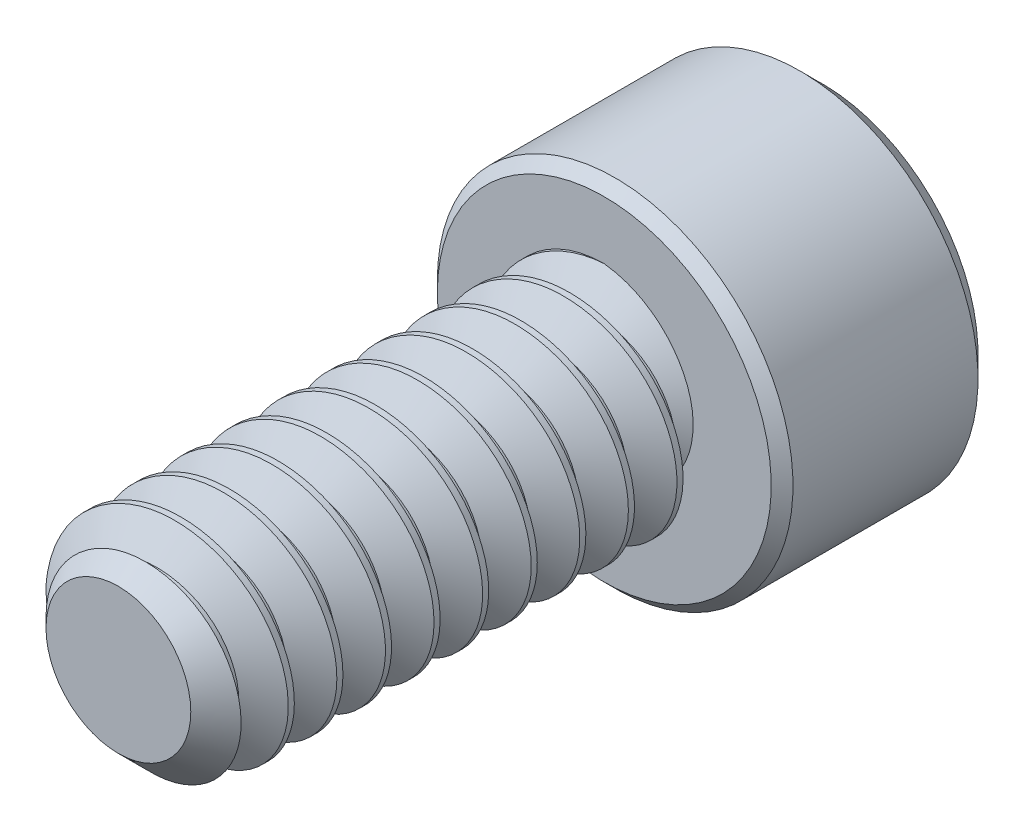
SolidWorks part; units mm, degrees
material "Alloy Steel"
ref_plane "Front Plane" through (0, 0, 0) normal (0, 0, 1) x (1, 0, 0)
ref_plane "Top Plane" through (0, 0, 0) normal (0, 1, 0) x (1, 0, 0)
ref_plane "Right Plane" through (0, 0, 0) normal (1, 0, 0) x (0, 0, -1)
sketch "Sketch1" plane through (0, 0, 0) normal (0, 0, 1) x (1, 0, 0)
  line L0 (0, 1.4224) -> (0, -1.4224) construction
  circle A0 centre (0, 0) radius 1.4224
  dimension "OD" = 2.8448
extrude "Extrude1" add sketch "Sketch1" against normal blind 6.35
sketch "Sketch2" plane through (0, 0, 0) normal (0, 0, 1) x (1, 0, 0)
  circle A0 centre (0, 0) radius 1.4224 construction
  circle A1 centre (0, 0) radius 1.4224
curve "Helix/Spiral1" pitch 0.635 height 6.985 radius 1.4224 centre (0, 0, 0) axis (0, 0, -1) start towards (0, 1, 0) parameters "pitch"=0.635
chamfer "Chamfer3" distance 0.4763 angle 45 1 edges at (1.4224, 0, 0)
sketch "Sketch3" plane through (0, 0, 0) normal (1, 0, 0) x (0, 0, -1)
  line L0 (-0.5556, 1.4224) -> (-0.3175, 1.01)
  line L1 (-0.3175, 1.01) -> (-0.2381, 1.01)
  line L2 (-0.2381, 1.01) -> (0, 1.4224)
  line L3 (-0.5556, 1.4224) -> (0, 1.4224)
  line L4 (-0.2778, 1.4224) -> (-0.2778, 1.01) construction
  line L5 (-0.4366, 1.2162) -> (-0.1191, 1.2162) construction
  line L6 (0, 1.4224) -> (0, -1.4224) construction
  dimension "D1" = 0.0794
  dimension "D2" = 0.3175
  dimension "D3" = 60
sweep "Cut-Sweep1" cut profiles "Sketch3" path "Helix/Spiral1"
sketch "Sketch6" plane through (0, 0, -6.35) normal (0, 0, -1) x (-1, 0, 0)
  circle A0 centre (0, 0) radius 2.3241
  dimension "head dia" = 4.6482
extrude "Extrude2" add sketch "Sketch6" along normal blind 2.8448
sketch "Sketch7" plane through (0, 0, -9.1948) normal (0, 0, -1) x (-1, 0, 0)
  line L1 (0, 1.3748) -> (-1.1906, 0.6874)
  line L2 (-1.1906, 0.6874) -> (-1.1906, -0.6874)
  line L3 (-1.1906, -0.6874) -> (0, -1.3748)
  line L4 (0, -1.3748) -> (1.1906, -0.6874)
  line L5 (1.1906, -0.6874) -> (1.1906, 0.6874)
  line L6 (1.1906, 0.6874) -> (0, 1.3748)
  circle A0 centre (0, 0) radius 1.1906 construction
  dimension "hex dia" = 2.3813
extrude "Cut-Extrude1" cut sketch "Sketch7" against normal blind 1.7859
sketch "Sketch8" plane through (0, 0, -9.1948) normal (0, 0, -1) x (-1, 0, 0)
  circle A0 centre (0, 0) radius 1.3748
extrude "Cut-Extrude2" cut sketch "Sketch8" against normal blind 0.2845 draft 45
chamfer "Chamfer1" distance 0.2845 angle 45 1 edges at (-2.3241, 0, -9.1948)
chamfer "Chamfer2" distance 0.1422 angle 45 1 edges at (-2.3241, 0, -6.35)
sketch "Sketch9" plane through (0, 0, 0) normal (1, 0, 0) x (0, 0, -1)
  line L0 (0, 1.4224) -> (0, -1.4224) construction
  line L1 (3.4925, 1.4224) -> (3.4925, -1.4224) construction
  line L2 (6.35, 2.3241) -> (6.35, -2.3241) construction
  line L3 (9.1948, 2.3241) -> (9.1948, -2.3241) construction
  line L4 (9.1948, 0) -> (0, 0) construction
  dimension "D1" = 3.4925
  dimension "D2" = 2.8448
  dimension "D3" = 4.6482
  dimension "D4" = 6.35
equation "\"D3@Helix/Spiral1\" = \"screw length@Extrude1\"+\"pitch@Helix/Spiral1\""
equation "\"D1@Sketch3\" = \"pitch@Helix/Spiral1\"*.125"
equation "\"D2@Sketch3\" = \"pitch@Helix/Spiral1\"*.5"
equation "\"D1@Cut-Extrude1\" = \"hex dia@Sketch7\"*.75"
equation "\"D1@Chamfer1\" = \"head depth@Extrude2\"/10"
equation "\"D1@Sketch9\" = \"pitch@Helix/Spiral1\"*5.5"
equation "\"D1@Chamfer2\" = \"D1@Chamfer1\"/2"
equation "\"D1@Cut-Extrude2\" = \"D1@Chamfer2\"*2"
equation "\"D1@Chamfer3\" = \"pitch@Helix/Spiral1\"*.750"
equation "\"D2@Sketch9\" = \"head depth@Extrude2\""
equation "\"D3@Sketch9\" = \"head dia@Sketch6\""
equation "\"D4@Sketch9\" = \"screw length@Extrude1\""
